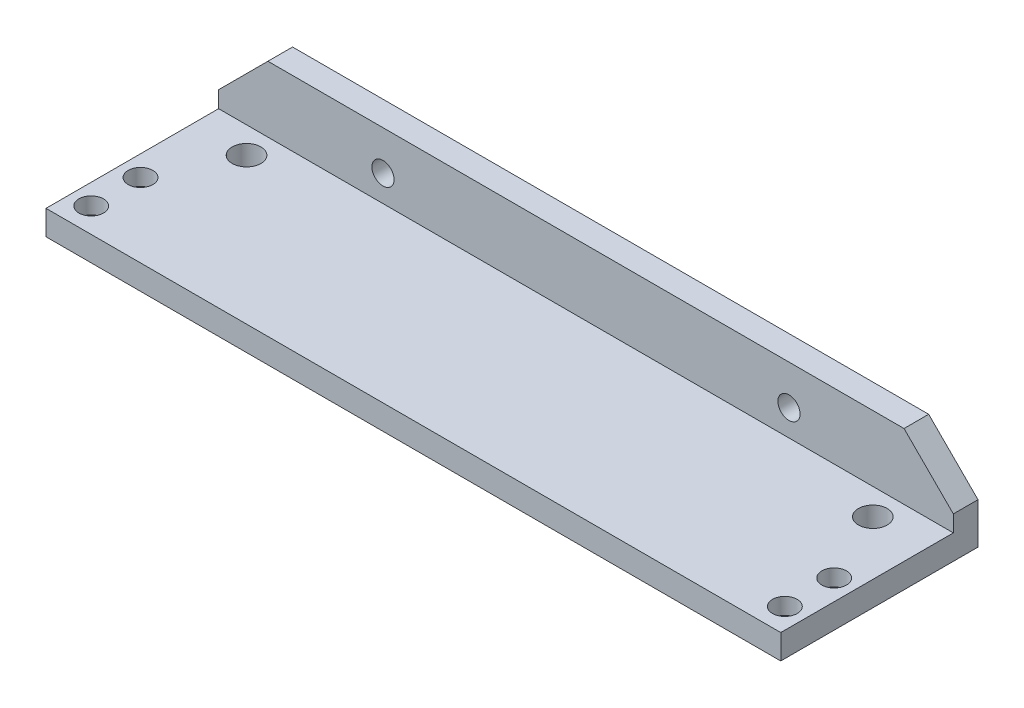
SolidWorks part; units mm, degrees
material "7075-T6, Plate (SS)"
ref_plane "Front Plane" through (0, 0, 0) normal (0, 0, 1) x (1, 0, 0)
ref_plane "Top Plane" through (0, 0, 0) normal (0, 1, 0) x (1, 0, 0)
ref_plane "Right Plane" through (0, 0, 0) normal (1, 0, 0) x (0, 0, -1)
sketch "Sketch1" plane through (0, 0, 0) normal (0, 0, 1) x (1, 0, 0)
  line L0 (-38.2511, 8.8926) -> (-38.2511, 0.8926)
  line L1 (-38.2511, 0.8926) -> (51.1489, 0.8926)
  line L2 (51.1489, 0.8926) -> (51.1489, 8.8926)
  line L3 (51.1489, 8.8926) -> (-38.2511, 8.8926)
  line L4 (-38.2511, 0.8926) -> (-38.2511, -2.1074)
  line L5 (-38.2511, -2.1074) -> (51.1489, -2.1074)
  line L6 (51.1489, -2.1074) -> (51.1489, 0.8926)
  line L7 (-38.2511, 2.8926) -> (-32.2511, 8.8926)
  line L8 (51.1489, 2.8926) -> (45.1489, 8.8926)
  circle A0 centre (-18.2511, 4.0926) radius 1.35
  circle A1 centre (31.1489, 4.0926) radius 1.35
  dimension "D2" = 2.7
  dimension "D3" = 2.7
  dimension "D1" = 89.4
  dimension "D4" = 3
  dimension "D5" = 8
  dimension "D6" = 3.2
  dimension "D7" = 3.2
  dimension "D8" = 20
  dimension "D9" = 20
  dimension "D10" = 6
  dimension "D11" = 6
  dimension "D12" = 6
  dimension "D13" = 6
extrude "Boss-Extrude1" add sketch "Sketch1" along normal blind 3 contours L2 L3 L0 L1 A1 A0 region at (6.4489, 4.7985, 0)
extrude "Boss-Extrude2" add sketch "Sketch1<3>" along normal blind 24 contours L5 L6 L1 L4 region at (6.4489, -0.6074, 0)
sketch "Sketch1<3>" plane through (0, 0, 0) normal (0, 0, 1) x (1, 0, 0) same geometry as "Sketch1"
sketch "Sketch3" plane through (0, 0.8926, 0) normal (0, 1, 0) x (1, 0, 0)
  line L0 (-38.2511, -3) -> (51.1489, -3) construction
  line L1 (45.1489, -3) -> (-32.2511, -3) construction
  line L2 (51.1489, -24) -> (51.1489, -3) construction
  line L3 (-38.2511, -24) -> (-38.2511, -3) construction
  line L4 (-38.2511, -24) -> (51.1489, -24) construction
  circle A2 centre (-31.6511, -6.2) radius 1.75
  circle A5 centre (44.5489, -6.2) radius 1.75
  circle A6 centre (-35.7511, -15) radius 1.5
  circle A7 centre (-35.7511, -21) radius 1.5
  circle A8 centre (48.6489, -15) radius 1.5
  circle A9 centre (48.6489, -21) radius 1.5
  circle A10 centre (-35.7511, -21) radius 2.25
  circle A11 centre (-35.7511, -15) radius 2.25
  circle A12 centre (48.6489, -21) radius 2.25
  circle A13 centre (48.6489, -15) radius 2.25
  dimension "D1" = 3.5
  dimension "D2" = 3.5
  dimension "D7" = 3
  dimension "D8" = 3
  dimension "D10" = 3
  dimension "D17" = 3
  dimension "D18" = 3
  dimension "D19" = 4.5
  dimension "D20" = 4.5
  dimension "D21" = 4.5
  dimension "D22" = 4.5
  dimension "D3" = 3.2
  dimension "D4" = 3.2
  dimension "D5" = 6.6
  dimension "D6" = 6.6
  dimension "D9" = 6
  dimension "D11" = 2.5
  dimension "D12" = 2.5
  dimension "D13" = 3
  dimension "D14" = 6
  dimension "D15" = 2.5
  dimension "D16" = 2.5
extrude "Cut-Extrude1" cut sketch "Sketch3" against normal up to next contours A8 | A9 | A6 | A7 | A5 | A2 region at (-35.7511, 0.8926, 15) region at (48.6489, 0.8926, 15) region at (48.6489, 0.8926, 21)
extrude "Cut-Extrude2" cut sketch "Sketch3<5>" along normal blind 1 from surface contours A11 A6 | A10 A7 | A13 | A12 region at (-37.9374, 0.8926, 21) region at (-37.9374, 0.8926, 15) starting at face at (44.5489, -2.1074, 7.95)
sketch "Sketch3<5>" plane through (0, 0.8926, 0) normal (0, 1, 0) x (1, 0, 0) same geometry as "Sketch3"
